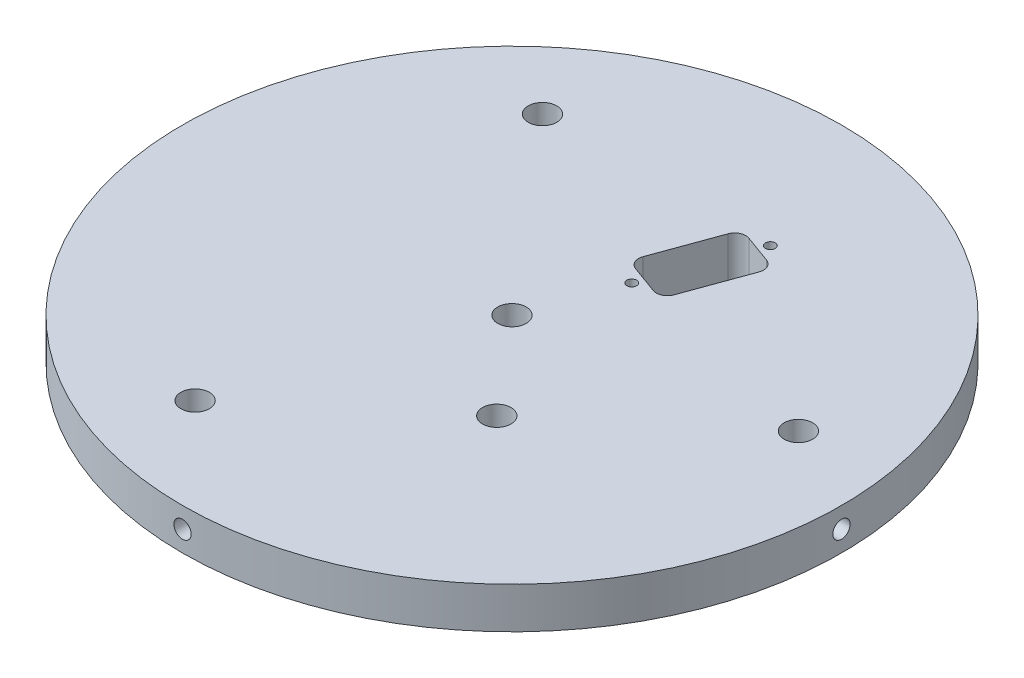
SolidWorks part; units mm, degrees
material "6061-T6 (SS)"
ref_plane "Front Plane" through (0, 0, 0) normal (0, 0, 1) x (1, 0, 0)
ref_plane "Top Plane" through (0, 0, 0) normal (0, 1, 0) x (1, 0, 0)
ref_plane "Right Plane" through (0, 0, 0) normal (1, 0, 0) x (0, 0, -1)
sketch "Sketch1" plane through (0, 0, 0) normal (0, 1, 0) x (1, 0, 0)
  line L0 (0, 0) -> (-50.3682, 60.0265)
  line L1 (0, 0) -> (50.3682, 60.0265)
  line L2 (0, 0) -> (0, 72.1431) construction
  circle A0 centre (0, 0) radius 78.359
  circle A1 centre (0, 0) radius 76.1746
  circle A2 centre (0, 0) radius 76.1746
  dimension "D1" = 156.718
  dimension "D2" = 152.3492
  dimension "D3" = 152.3492
  dimension "D4" = 80
extrude "Boss-Extrude1" add sketch "Sketch1" along normal blind 25.4 contours L2 A2 L1 A0 | L2 A1 L1 A2 | L2 A2 L1 A1 | L2 A0 L1 A2 | A2 L2 A1 L0 | A0 L2 A2 L0 | A2 L2 A0 L0 | A1 L2 A2 L0 region at (0, 0, 13.3592) region at (-23.5316, 0, -29.974) region at (-33.0764, 0, 70.9325) region at (-48.8794, 0, -59.85)
ref_plane "Plane1" through (0, 12.7, 0) normal (0, 1, 0) x (1, 0, 0)
sketch "Sketch6" plane through (0, 25.4, 0) normal (0, 1, 0) x (1, 0, 0)
  circle A0 centre (0, 0) radius 76.1746
  dimension "D1" = 152.3492
extrude "Boss-Extrude5" add sketch "Sketch6" along normal blind 9.525
sketch "Sketch7" plane through (0, 0, 0) normal (0, -1, 0) x (1, 0, 0)
  circle A0 centre (0, 0) radius 76.1746
  dimension "D1" = 152.3492
extrude "Boss-Extrude6" add sketch "Sketch7" along normal blind 9.525
sketch "Sketch8" plane through (0, -9.525, 0) normal (0, -1, 0) x (1, 0, 0)
  circle A0 centre (0, 0) radius 73.025
  dimension "D1" = 146.05
extrude "Cut-Extrude5" cut sketch "Sketch8" against normal up to surface (34.925 mm away) up to face at (0, 25.4, 76.1746)
ref_plane "Plane2" through (0, 0, -76.1746) normal (0, 0, -1) x (-1, 0, 0)
ref_plane "Plane5" through (0, 25.4, 0) normal (0, 1, 0) x (1, 0, 0)
ref_axis "Axis1" through (0, 0, 0) along (0, 1, 0)
sketch "Sketch3" plane through (0, 0, -76.1746) normal (0, 0, -1) x (-1, 0, 0)
  line L4 (76.1746, 0) -> (-76.1746, 0)
  line L5 (-76.1746, -9.525) -> (76.1746, -9.525)
  line L6 (76.1746, 25.4) -> (-76.1746, 25.4)
  line L7 (76.1746, 34.925) -> (-76.1746, 34.925)
  line L8 (0, 34.925) -> (0, 25.4) construction
  line L9 (0, 0) -> (0, -9.525) construction
  circle A0 centre (0, 30.1625) radius 2
  circle A1 centre (0, -4.7625) radius 2
  point P12 (0, 30.1625)
  point P13 (0, -4.7625)
  point P14 (-77.5445, 179.1871)
  dimension "D1" = 4
extrude "Cut-Extrude2" cut sketch "Sketch3" against normal blind 9.525 contours L8 A0 | L8 A0 | L9 A1 | L9 A1 region at (0, 30.1625, -76.1746) region at (0, -4.7625, -76.1746)
extrude "Cut-Extrude3" cut sketch "Sketch1<7>" against normal blind 9.525 from surface contours L2 A1 L1 A2 | A1 L2 A2 L0 | A2 L2 A0 L0 | L2 A2 L1 A0 region at (-23.5316, 0, -29.974) region at (-48.8794, 0, -59.85) starting at plane "Plane5"
sketch "Sketch1<7>" plane through (0, 0, 0) normal (0, 1, 0) x (1, 0, 0) same geometry as "Sketch1"
pattern_circular "CirPattern2" count 3 over 360 about axis through (0, 0, 0) along (0, 1, 0) of "Cut-Extrude3"
ref_plane "Plane3" through (0, 34.925, 0) normal (0, 1, 0) x (1, 0, 0)
sketch "Sketch4" plane through (0, 34.925, 0) normal (0, 1, 0) x (1, 0, 0)
  circle A0 centre (0, 0) radius 73.025
  dimension "D1" = 146.05
extrude "Boss-Extrude4" add sketch "Sketch4" against normal blind 9.525
pattern_circular "CirPattern3" count 4 over 360 about axis through (0, 0, 0) along (0, 1, 0) of "Cut-Extrude2"
sketch "Sketch9" plane through (0, 34.925, 0) normal (0, 1, 0) x (1, 0, 0)
  line L0 (0, 0) -> (-26.8004, -73.6334) construction
  line L1 (0, 0) -> (32.0596, -38.2071) construction
  circle A0 centre (0, 0) radius 3.3
  circle A1 centre (-19.5465, -53.7034) radius 3.3
  circle A2 centre (-36.7353, 43.7794) radius 3.3
  circle A3 centre (56.2818, 9.924) radius 3.3
  circle A4 centre (18.3677, -21.8897) radius 3.3
  point P15 (0, 0)
  dimension "D1" = 6.6
  dimension "D2" = 6.6
  dimension "D6" = 6.6
  dimension "D3" = 57.15
  dimension "D4" = 60
  dimension "D7" = 28.575
extrude "Cut-Extrude6" cut sketch "Sketch9" against normal through all
sketch "Sketch10" plane through (0, 25.4, 0) normal (0, 1, 0) x (1, 0, 0)
  circle A0 centre (0, 0) radius 82.3228
extrude "Cut-Extrude7" cut sketch "Sketch10" against normal through all
hole_wizard "Tap Drill for #4-40 Tap1" positions "Sketch12" profile "Sketch13" hole size "#4-40" standard "ANSI Inch" end condition through all
sketch "Sketch12" plane through (0, 34.925, 0) normal (0, 1, 0) x (1, 0, 0)
  line L0 (0, 0) -> (18.6243, 51.1699) construction
  line L2 (0, 0) -> (-36.7353, 43.7794) construction
  circle A0 centre (0, 0) radius 21.59 construction
  point P0 (7.3842, 20.288)
  point P2 (15.9347, 43.7803)
  dimension "D3" = 43.18
  dimension "D1" = 60
  dimension "D2" = 25
sketch "Sketch13" plane through (7.3842, 34.925, -20.288) normal (1, 0, 0) x (0, 0, 1)
  line L0 (0, 0) -> (0, 9.525)
  line L1 (0, 9.525) -> (1.1303, 9.525)
  line L2 (1.1303, 9.525) -> (1.1303, 0)
  line L5 (1.1303, 0) -> (0, 0)
  line L11 (0, -6.35) -> (0, 107.95) construction
  dimension "Thru Hole Dia." = 2.2606
  dimension "Thru Hole Depth" = 9.525
sketch "Sketch14" plane through (0, 34.925, 0) normal (0, 1, 0) x (1, 0, 0)
  line L0 (7.3842, 20.288) -> (15.9347, 43.7803) construction
  line L1 (14.6438, 22.7814) -> (19.8932, 37.2038)
  line L2 (11.3883, 21.2633) -> (4.9439, 23.6089)
  line L3 (18.3751, 40.4594) -> (11.9307, 42.8049)
  line L4 (3.4258, 26.8644) -> (8.6751, 41.2868)
  arc A0 (19.8932, 37.2038) -> (18.3751, 40.4594) centre (17.5063, 38.0725) ccw
  arc A1 (11.9307, 42.8049) -> (8.6751, 41.2868) centre (11.0619, 40.4181) ccw
  arc A2 (11.3883, 21.2633) -> (14.6438, 22.7814) centre (12.257, 23.6501) ccw
  arc A3 (4.9439, 23.6089) -> (3.4258, 26.8644) centre (5.8126, 25.9957) cw
  point P0 (8.1661, 22.4361)
  dimension "D4" = 2.54
  dimension "D5" = 2.54
  dimension "D1" = 2.286
  dimension "D2" = 2.286
  dimension "D3" = 11.938
extrude "Cut-Extrude9" cut sketch "Sketch14" against normal through all
equation "\"AB_Coupler_OD_Length\"= 1in"
equation "\"AB_Coupling_Section_Length\"= 0.375in"
equation "\"AB_Coupler_Length\"= \"AB_Coupler_OD_Length\" + \"AB_Coupling_Section_Length\" * 2"
equation "\"Cutout_Angle\" = 80"
equation "\"AB_Coupler_Num_Screws\"= 6"
equation "\"Num_Cutouts\" = 3"
equation "\"AB_Coupler_OD\"= 6.17in"
equation "\"AB_Coupler_ID\"= 5.75in"
equation "\"AB_Coupler_Surface_Diameter\"= 5.998in"
equation "\"D2@Sketch1\"=\"Bodytube_ID\""
equation "\"AB_Coupling_Screw_Diameter\"= 0.1065in"
equation "\"Aft_Section_Length\"= 39in"
equation "\"Aft_Lower_Length\"= 22in"
equation "\"Aft_Upper_Length\"= \"Aft_Section_Length\" - \"Aft_Lower_Length\" - \"AB_Coupler_OD_Length\""
equation "\"Mid_Coupler_Length\" = 13in"
equation "\"Lead_Screw_Dist\" = 3.4in"
equation "\"Lead_Screw_Diam\" = 11mm"
equation "\"Lead_Screw_Length\" = (\"Mid_Coupler_Length\" + 2*0.375in + 2*0.5in)"
equation "\"Bodytube_OD\" = 6.17in"
equation "\"Paddle_Pin_Offset\" = .25in"
equation "\"Bodytube_ID\" = 5.998in"
equation "\"Paddle_Pin_Radius\" = 2.25in"
equation "\"D1@Sketch4\"=\"AB_Coupler_ID\""
equation "\"D1@Sketch6\"=\"AB_Coupler_Surface_Diameter\""
equation "\"D1@Boss-Extrude5\"=\"AB_Coupling_Section_Length\""
equation "\"D1@Sketch7\"=\"AB_Coupler_Surface_Diameter\""
equation "\"D1@Boss-Extrude6\"=\"AB_Coupling_Section_Length\""
equation "\"D1@Sketch8\"=\"AB_Coupler_ID\""
equation "\"D3@Sketch9\"=\"Paddle_Pin_Radius\""
equation "\"Motor_OD\" = 4in"
equation "\"Fwd_Tube_Length\" = 40in"
equation "\"Mid_Tube_Length\" = 1in"
equation "\"AB_Paddle_Height\" = 0.375in"
equation "\"AB_Central_Bushing_Length\" = .75in"
equation "\"Paddle_Gear_OD\" = 3.2in"
equation "\"Fwd_BKHD_From_Top\" = 18in"
equation "\"Fin_Thickness\"= .118in"
equation "\"Guiderail_Cutout_Diameter\"= 1.5in"
equation "\"DB9_Hole_Dist\" = 25mm"
equation "\"D2@Sketch12\"=\"DB9_Hole_Dist\""
equation "\"Drive_Gear_OD\" = 1.7in"
equation "\"D3@Sketch12\"=\"Drive_Gear_OD\""
equation "\"DB9_Relief_Width\" = 0.47in"
equation "\"D3@Sketch14\"=\"DB9_Relief_Width\""
equation "\"DB9_Relief_Hole_Offset\" = 0.09in"
equation "\"D2@Sketch14\"=\"DB9_Relief_Hole_Offset\""
equation "\"D1@Sketch14\"=\"DB9_Relief_Hole_Offset\""
equation "\"SS_Paddle_Pin_Radius\" = 2.25*0.66in"
equation "\"Airbrakes_Wire_Hole_Dia\" = .25in"
equation "\"Airbrakes_Wire_Hole_Dist\" = 1.1in"
equation "\"Servo_Gear_Offset\" = 0.5in"
